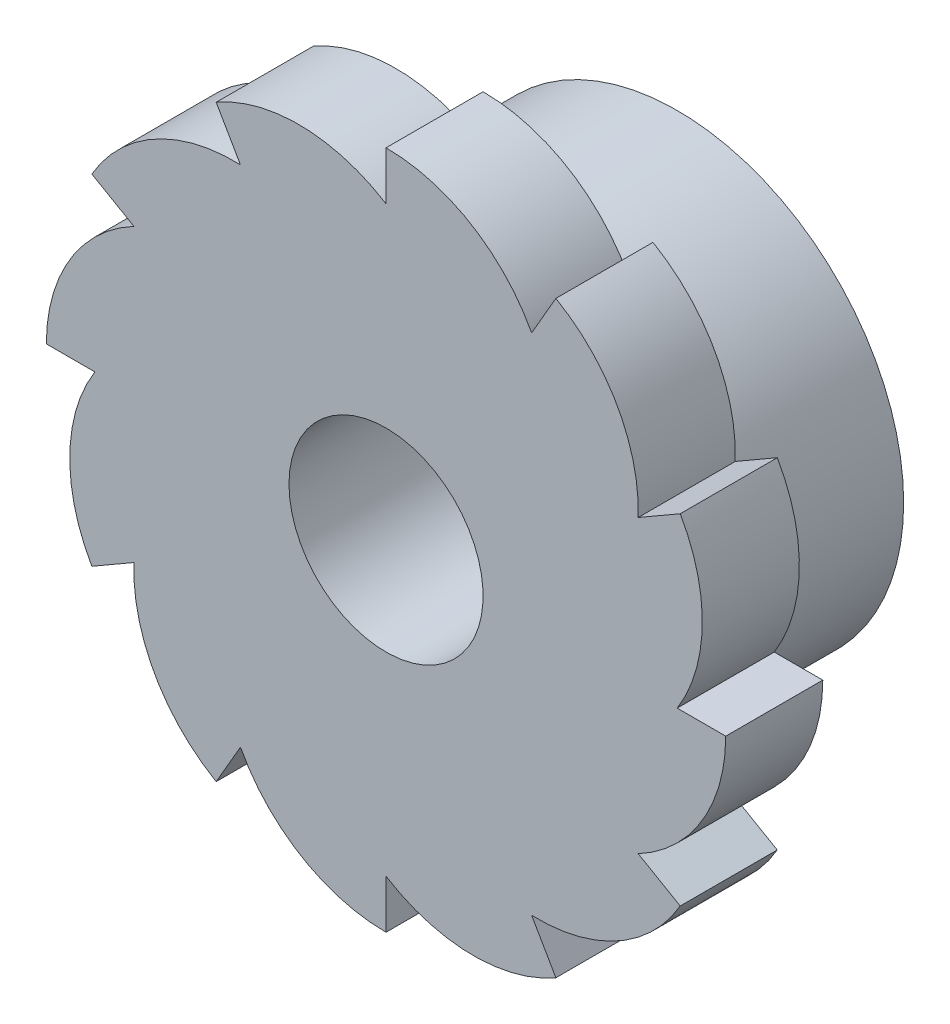
SolidWorks part; units mm, degrees
ref_plane "Front Plane" through (0, 0, 0) normal (0, 0, 1) x (1, 0, 0)
ref_plane "Top Plane" through (0, 0, 0) normal (0, 1, 0) x (1, 0, 0)
ref_plane "Right Plane" through (0, 0, 0) normal (1, 0, 0) x (0, 0, -1)
sketch "Sketch1" plane through (0, 0, 0) normal (0, 0, 1) x (1, 0, 0)
  line L0 (0, 9) -> (0, 10.5)
  line L1 (0.0027, 10.5) -> (-49999.9973, 10.5) construction
  line L2 (0, 0) -> (0, 50000) construction
  line L3 (-0.0178, -0.0309) -> (24999.9822, 43301.2393) construction
  line L4 (0, 9) -> (0, 3)
  line L5 (4.5, 7.7942) -> (1.5, 2.5981)
  circle A0 centre (0, 0) radius 9 construction
  circle A1 centre (0, 0) radius 3 construction
  arc A2 (0, 10.5) -> (4.5, 7.7942) centre (0, 5.4051) cw
  arc A3 (0, 3) -> (1.5, 2.5981) centre (0, 0) cw
  dimension "D1" = 6
  dimension "D2" = 18
  dimension "D3" = 30
  dimension "D4" = 1.5
extrude "Boss-Extrude1" add sketch "Sketch1" along normal blind 3
pattern_circular "CirPattern1" count 12 over 360 about axis through (0, 0, 3) along (0, 0, -1) of "Boss-Extrude1"
sketch "Sketch3" plane through (0, 0, 0) normal (0, 0, -1) x (-1, 0, 0)
  line L0 (7, 0) -> (7, -7)
  line L2 (-7, 0) -> (-7, 7)
  line L3 (-7, 7) -> (7, 7)
  line L4 (7, 0) -> (7, 7)
  line L5 (7, -7) -> (0, -7)
  arc A0 (7, 0) -> (0, -7) centre (0, 0) ccw construction
  arc A1 (0, -7) -> (-7, 0) centre (0, 0) cw
  circle A2 centre (0, 0) radius 3
  circle A3 centre (0, 0) radius 3 construction
  dimension "D1" = 14
extrude "Boss-Extrude2" add sketch "Sketch3" along normal blind 6
sketch "Sketch4" plane through (0, 7, 0) normal (0, 1, 0) x (1, 0, 0)
  line L0 (-3, 0) -> (3, 0) construction
  line L1 (-3, 0) -> (3, 0) construction
  line L2 (-3, 0) -> (-3, -50000) construction
  line L3 (-7, 6) -> (-7, 0) construction
  line L4 (-7, 3) -> (-3, 3) construction
  circle A0 centre (-5, 3) radius 1.25
  point P10 (-5, 3)
  dimension "D1" = 2.5
extrude "Cut-Extrude1" cut sketch "Sketch4" against normal through all contours A0
sketch "Sketch6" plane through (-7, 0, 0) normal (-1, 0, 0) x (0, 0, 1)
  line L0 (0, 0) -> (-50000, 0) construction
  line L1 (-6, -0.2) -> (-6, 0.2)
  line L2 (-6, -7) -> (-6, 7) construction
  line L3 (-6, 0.2) -> (-2.5, 0.2)
  line L4 (-2.5, 0.2) -> (-2.5, 0.4)
  line L5 (-2.5, 0.4) -> (-0.5, 0.4)
  line L6 (-0.5, 0.4) -> (-0.5, -0.4)
  line L8 (-2.5, -0.4) -> (-0.5, -0.4)
  line L9 (-2.5, -0.2) -> (-2.5, -0.4)
  line L10 (-6, -0.2) -> (-2.5, -0.2)
  point P12 (-0.5, 0)
  point P15 (-6, 0)
  dimension "D1" = 5.5
  dimension "D2" = 3.5
  dimension "D3" = 0.4
  dimension "D4" = 0.2
extrude "Cut-Extrude3" cut sketch "Sketch6" against normal up to next
fillet "Fillet2" radius 0.1 8 edges at (-6.5728, 0.4, -2.5) (-3.4238, 0.2, -2.5) (-3.4138, 0.4, -2.5) (-6.5728, 0.2, -2.5) (-3.4138, -0.4, -2.5) (-3.4238, -0.2, -2.5) (-6.5728, -0.4, -2.5) (-6.5728, -0.2, -2.5)
fillet "Fillet3" radius 0.3 2 edges at (-4.9866, -0.4, -0.5) (-4.9866, 0.4, -0.5)
sketch "Sketch7" plane through (0, 0, -6) normal (0, 0, -1) x (-1, 0, 0)
  line L1 (-7, 7) -> (7, 7)
  line L2 (-7, 7) -> (-7, 0)
  line L3 (0, -7) -> (7, -7)
  line L4 (7, 7) -> (7, -7)
  arc A0 (0, -7) -> (-7, 0) centre (0, 0) ccw
  line M6 (7, -7) -> (7, -0.2)
  line M7 (7, -0.2) -> (2.9933, -0.2)
  line M9 (2.9933, 0.2) -> (7, 0.2)
  line M10 (7, 0.2) -> (7, 7)
  line M11 (7, 7) -> (-7, 7)
  line M12 (-7, 7) -> (-7, 0)
  line M14 (0, -7) -> (7, -7)
extrude "Cut-Extrude4" cut sketch "Sketch7" against normal up to surface (6 mm away) contours A0 L1 M12 | A0 M9 M10 M11 | A0 M14 M6 M7 region at (-5.4364, 5.4365, -6) region at (5.4364, 5.4364, -6) region at (-5.4364, -5.4365, -6) up to face at (0.2899, -0.2899, 0)
equation "\"ratchetTeethCount\"= 12"
equation "\"D3@Sketch1\"=360/\"ratchetTeethCount\""
equation "\"D1@CirPattern1\"=\"ratchetTeethCount\""
equation "\"ratchetHeight\"=1.5"
equation "\"D4@Sketch1\"=\"ratchetHeight\""
equation "\"ratchetInnerDiameter\"= 18"
equation "\"D2@Sketch1\"=\"ratchetInnerDiameter\""
